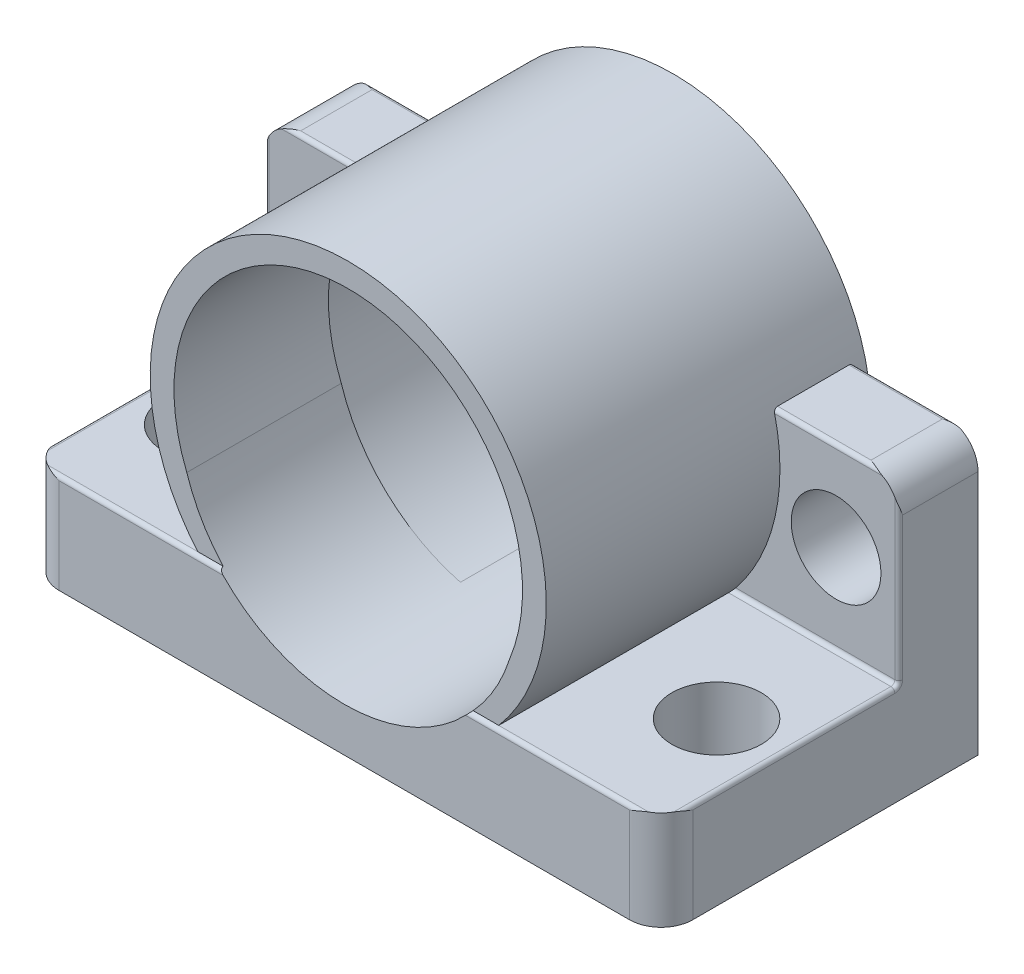
SolidWorks part; units mm, degrees
ref_plane "Front Plane" through (0, 0, 0) normal (0, 0, 1) x (1, 0, 0)
ref_plane "Top Plane" through (0, 0, 0) normal (0, 1, 0) x (1, 0, 0)
ref_plane "Right Plane" through (0, 0, 0) normal (1, 0, 0) x (0, 0, -1)
sketch "Sketch1" plane through (0, 0, 0) normal (0, 1, 0) x (1, 0, 0)
  line L1 (-80, -40) -> (80, -40)
  line L2 (-80, -40) -> (-80, 40)
  line L3 (-80, 40) -> (80, 40)
  line L4 (80, -40) -> (80, 40)
  line L5 (-80, -40) -> (80, 40) construction
  line L6 (-80, 40) -> (80, -40) construction
  point P1 (0, 0)
extrude "Boss-Extrude1" add sketch "Sketch1" along normal blind 25
sketch "Sketch2" plane through (0, 25, 0) normal (0, 1, 0) x (1, 0, 0)
  line L0 (0, 0) -> (0, 40) construction
  line L1 (80, 40) -> (-80, 40) construction
  line L2 (0, 40) -> (-80, 40) construction
  line L3 (-80, 40) -> (-80, -40) construction
  line L4 (-80, 40) -> (-80, 20) construction
  line L5 (-80, 20) -> (0, 20) construction
  line L6 (0, 20) -> (80, 20) construction
  line L7 (80, -40) -> (80, 40) construction
  line L8 (80, 20) -> (80, 40) construction
  line L9 (80, 40) -> (0, 40) construction
  line L10 (0, 40) -> (-40, 40) construction
  line L11 (-40, 40) -> (-40, 20) construction
  line L12 (-80, 20) -> (-40, 20)
  line L13 (-40, 40) -> (-38, 40)
  line L14 (-40, 40) -> (-80, 40)
  line L15 (0, 20) -> (40, 20) construction
  line L16 (40, 20) -> (40, 40) construction
  line L17 (40, 40) -> (0, 40) construction
  line L19 (40, 20) -> (80, 20)
  line L20 (80, 20) -> (80, 40)
  line L21 (80, 40) -> (40, 40)
  line L22 (40, 20) -> (38, 20)
  line L23 (38, 20) -> (38, 40)
  line L24 (38, 40) -> (40, 40)
  line L25 (-40, 20) -> (-38, 20)
  line L26 (-38, 20) -> (-38, 40)
  dimension "D1" = 20
sketch "Sketch6" plane through (0, 0, 0) normal (0, 0, 1) x (1, 0, 0)
  line L0 (0, 0) -> (0, 90) construction
  line L1 (0, -13.75) -> (0, 13.75) construction
  line L2 (0, 25) -> (0, 90) construction
  line L3 (40, 25) -> (0, 25) construction
  circle A0 centre (0, 57.5) radius 45
  dimension "D1" = 90
extrude "Boss-Extrude2" add sketch "Sketch2" along normal blind 45
fillet "Fillet1" radius 1 13 edges at (80, 47.5, -20) (-59, 25, -20) (59, 25, -20) (80, 25, 10) (-80, 0, 0) (0, 25, 40) (-80, 25, 10) (-80, 35, -40) (-80, 47.5, -20) (-59, 70, -20) (-59, 70, -40) (59, 70, -40) (59, 70, -20)
extrude "Extrude-Thin2" add sketch "Sketch6" against normal blind 43 and the other way blind 39 thin contours A0
sketch "Sketch7" plane through (0, 0, 0) normal (0, 0, 1) x (1, 0, 0)
  line L0 (0, 24.8513) -> (-58.5, 25) construction
  line L1 (0, -38.5) -> (0, 38.5) construction
  line L2 (-38, 25) -> (-79, 25) construction
  line L3 (-58.5, 25) -> (-29.25, 24.9257) construction
  line L4 (-43.6175, 51.7105) -> (-49.6637, 51.7105)
  arc A0 (-42.4706, 69) -> (-38, 35.3189) centre (0, 57.5) ccw construction
  arc A1 (-48.6595, 69) -> (-38.8298, 26) centre (0, 57.5) ccw construction
  circle A2 centre (0, 53.8683) radius 42.7639
extrude "Cut-Extrude2" cut sketch "Sketch7" against normal blind 39 and the other way blind 51 contours A2
sketch "Sketch9" plane through (0, 0, 0) normal (0, 0, 1) x (1, 0, 0)
  line L0 (-63.8298, 69) -> (-63.8298, 26) construction
  line L1 (-48.6595, 69) -> (-79, 69) construction
  line L2 (-79, 26) -> (-38.8298, 26) construction
  circle A0 centre (-63.8298, 47.5) radius 11.3303
  circle A1 centre (64.1702, 47.5) radius 11.3303
  dimension "D1" = 2
sketch "Sketch10" plane through (0, 25, 0) normal (0, 1, 0) x (1, 0, 0)
  line L0 (0, 0) -> (-79, 0) construction
  line L3 (-79, 19) -> (-79, -39) construction
  line L4 (-79, 0) -> (-79, -10) construction
  line L5 (-79, -10) -> (0, -10) construction
  line L6 (0, -10) -> (0, 0) construction
  line L7 (0, 0) -> (-39.5, 0) construction
  line L8 (-39.5, 0) -> (-39.5, -10) construction
  line L9 (-39.5, -10) -> (-59.5, -10) construction
  line L10 (-59.5, -10) -> (-69.5, -10) construction
  line L11 (-69.5, -10) -> (-64.5, -10) construction
  circle A2 centre (-64.5, -10) radius 11.3
  circle A3 centre (64, -10) radius 11.3
  dimension "D1" = 2
extrude "Cut-Extrude4" cut sketch "Sketch9" against normal through all
extrude "Cut-Extrude5" cut sketch "Sketch10" against normal through all
fillet "Fillet4" radius 8 4 edges at (80, 12, 40) (-80, 12.5, 40) (80, 70, -30) (-80, 70, -30)
sketch "Sketch12" plane through (0, 0, 0) normal (0, 0, 1) x (1, 0, 0)
  line L0 (0, 11.1537) -> (0, 101.5247) construction
  line L1 (0, -44) -> (0, 44) construction
  circle A0 centre (0, 56.3392) radius 45.1608
extrude "Cut-Extrude10" cut sketch "Sketch12" against normal through all
